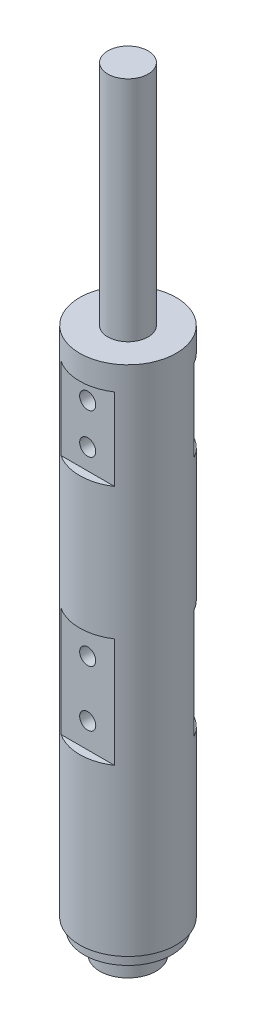
SolidWorks part; units mm, degrees
ref_plane "Front Plane" through (0, 0, 0) normal (0, 0, 1) x (1, 0, 0)
ref_plane "Top Plane" through (0, 0, 0) normal (0, 1, 0) x (1, 0, 0)
ref_plane "Right Plane" through (0, 0, 0) normal (1, 0, 0) x (0, 0, -1)
sketch "Sketch1" plane through (0, 0, 0) normal (0, 1, 0) x (1, 0, 0)
  circle A0 centre (0, 0) radius 19.05
  dimension "D1" = 38.1
extrude "Boss-Extrude1" add sketch "Sketch1" along normal blind 304.8
sketch "Sketch2" plane through (0, 0, 0) normal (0, 0, 1) x (1, 0, 0)
  line L0 (19.05, 0) -> (11.1125, 0)
  line L1 (11.1125, 0) -> (11.1125, 8.636)
  line L2 (11.1125, 8.636) -> (17.272, 8.636)
  line L3 (17.272, 8.636) -> (17.272, 12.954)
  line L4 (17.272, 12.954) -> (19.05, 12.954)
  line L5 (19.05, 0) -> (19.05, 304.8) construction
  line L6 (19.05, 304.8) -> (19.05, 215.011)
  line L7 (19.05, 304.8) -> (-19.05, 304.8) construction
  line L8 (19.05, 304.8) -> (-19.05, 304.8) construction
  line L9 (19.05, 215.011) -> (7.9375, 215.011)
  line L10 (7.9375, 215.011) -> (7.9375, 304.8)
  line L11 (7.9375, 304.8) -> (19.05, 304.8)
  line L12 (19.05, 0) -> (19.05, 12.954)
  line L13 (0, 348.3373) -> (0, -79.5423) construction
  dimension "D1" = 11.1125
  dimension "D2" = 17.272
  dimension "D3" = 8.636
  dimension "D4" = 4.318
  dimension "D5" = 7.9375
  dimension "D8" = 206.375
revolve "Cut-Revolve1" cut sketch "Sketch2" angle 360 about L13
sketch "Sketch3" plane through (0, 0, 0) normal (1, 0, 0) x (0, 0, -1)
  line L0 (0, 334.7642) -> (0, -20.7307) construction
  line L1 (19.05, 12.954) -> (19.05, 215.011) construction
  line L2 (19.05, 205.486) -> (9.525, 205.486)
  line L3 (19.05, 205.486) -> (19.05, 173.228)
  line L4 (19.05, 173.228) -> (9.525, 173.228)
  line L5 (9.525, 205.486) -> (9.525, 173.228)
  line L6 (19.05, 12.954) -> (19.05, 215.011) construction
  line L7 (19.05, 121.158) -> (9.525, 121.158)
  line L8 (19.05, 121.158) -> (19.05, 77.978)
  line L9 (19.05, 77.978) -> (9.525, 77.978)
  line L10 (9.525, 121.158) -> (9.525, 77.978)
  line L11 (62.8261, 109.982) -> (-27.1107, 109.982) construction
  line L12 (56.0678, 189.357) -> (-35.4285, 189.357) construction
  line L13 (19.05, 215.011) -> (-19.05, 215.011) construction
  line L14 (-19.05, 205.486) -> (-19.05, 173.228)
  line L15 (-19.05, 121.158) -> (-19.05, 77.978)
  line L16 (-19.05, 205.486) -> (-15.875, 205.486)
  line L17 (-15.875, 205.486) -> (-15.875, 173.228)
  line L18 (-15.875, 173.228) -> (-19.05, 173.228)
  line L19 (-19.05, 121.158) -> (-15.875, 121.158)
  line L20 (-15.875, 121.158) -> (-15.875, 77.978)
  line L21 (-15.875, 77.978) -> (-19.05, 77.978)
  dimension "D1" = 43.18
  dimension "D2" = 32.258
  dimension "D3" = 11.176
  dimension "D4" = 79.375
  dimension "D5" = 9.525
  dimension "D6" = 9.525
  dimension "D7" = 3.175
extrude "Cut-Extrude1" cut sketch "Sketch3" against normal through all and the other way through all
hole_wizard "1 (1) Diameter Hole1" positions "Sketch5" profile "Sketch6" hole size "1" standard "ANSI Inch" end condition through all
sketch "Sketch5" plane through (0, 0, -9.525) normal (0, 0, -1) x (-1, 0, 0)
  line L0 (0, 325.237) -> (0, -21.1805) construction
  line L1 (-16.4978, 121.158) -> (16.4978, 121.158) construction
  line L3 (-16.4978, 173.228) -> (-16.4978, 205.486) construction
  line L4 (-16.4978, 173.228) -> (-16.4978, 205.486) construction
  line L5 (-16.4978, 189.357) -> (10.79, 189.357) construction
  point P18 (0, 197.2945)
  point P20 (0, 181.4195)
  point P22 (0, 109.982)
  point P24 (0, 87.884)
  dimension "D1" = 11.176
  dimension "D2" = 22.098
  dimension "D3" = 15.875
sketch "Sketch6" plane through (0, 197.2945, -9.525) normal (1, 0, 0) x (0, 1, 0)
  line L0 (0, 0) -> (0, 28.575)
  line L1 (0, 28.575) -> (3.175, 28.575)
  line L2 (3.175, 28.575) -> (3.175, 0)
  line L5 (3.175, 0) -> (0, 0)
  line L11 (0, -6.35) -> (0, 107.95) construction
  dimension "Thru Hole Dia." = 6.35
  dimension "Thru Hole Depth" = 28.575
